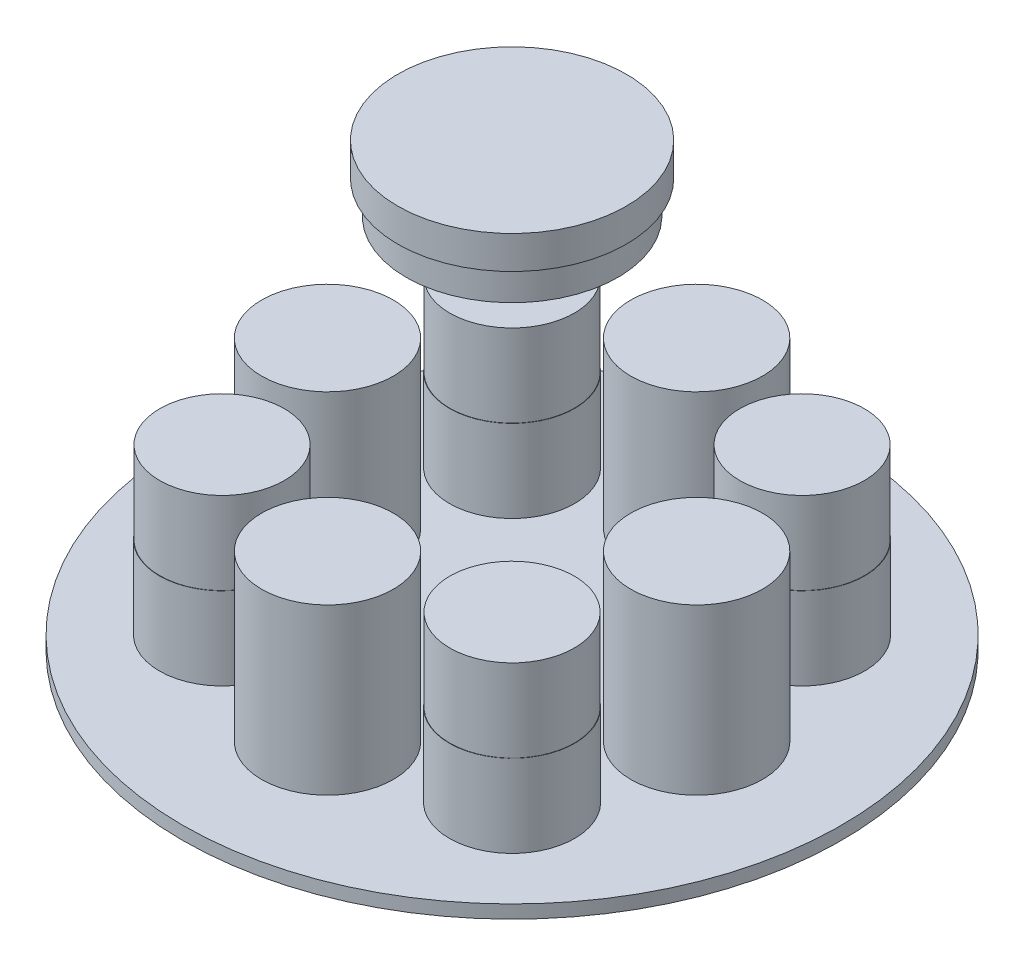
SolidWorks part; units mm, degrees
ref_plane "Front Plane" through (0, 0, 0) normal (0, 0, 1) x (1, 0, 0)
ref_plane "Top Plane" through (0, 0, 0) normal (0, 1, 0) x (1, 0, 0)
ref_plane "Right Plane" through (0, 0, 0) normal (1, 0, 0) x (0, 0, -1)
sketch "Sketch1" plane through (0, 0, 0) normal (0, 1, 0) x (1, 0, 0)
  circle A0 centre (0, 0) radius 50
  dimension "D1" = 100
extrude "Boss-Extrude1" add sketch "Sketch1" along normal blind 2 contours A0
sketch "Sketch2" plane through (0, 2, 0) normal (0, 1, 0) x (1, 0, 0)
  line L0 (-55, 0) -> (55, 0) construction
  circle A0 centre (28, 0) radius 10
  circle A1 centre (0, 28) radius 10
  circle A2 centre (-28, 0) radius 10
  circle A3 centre (0, -28) radius 10
  circle A5 centre (22, -22) radius 9.5
  circle A6 centre (-22, -22) radius 9.5
  circle A7 centre (22, 22) radius 9.5
  circle A8 centre (-22, 22) radius 9.5
  dimension "D1" = 20
  dimension "D2" = 20
  dimension "D3" = 20
  dimension "D4" = 20
  dimension "D9" = 19
  dimension "D10" = 19
  dimension "D5" = 28
  dimension "D6" = 28
  dimension "D7" = 28
  dimension "D8" = 28
  dimension "D11" = 22
  dimension "D12" = 22
  dimension "D13" = 22
  dimension "D14" = 22
extrude "Boss-Extrude2" add sketch "Sketch2" along normal blind 25 contours A1 | A0 | A3 | A2 region at (28, 2, 0) region at (0, 2, -28) region at (-28, 2, 0) region at (0, 2, 28)
extrude "Boss-Extrude3" add sketch "Sketch2<3>" along normal blind 12.5 contours A5 | A7 | A8 | A6 region at (22, 2, 22) region at (-22, 2, 22) region at (22, 2, -22) region at (-22, 2, -22)
sketch "Sketch2<3>" plane through (0, 2, 0) normal (0, 1, 0) x (1, 0, 0) same geometry as "Sketch2"
sketch "Sketch5" plane through (0, 14.5, 0) normal (0, 1, 0) x (1, 0, 0)
  circle A0 centre (-22, -22) radius 9.45
  circle A1 centre (22, 22) radius 9.45
  circle A2 centre (22, -22) radius 9.45
  circle A3 centre (-22, 22) radius 9.45
  dimension "D1" = 18.9
  dimension "D2" = 18.9
  dimension "D3" = 18.9
  dimension "D4" = 18.9
extrude "Boss-Extrude4" add sketch "Sketch5" along normal blind 12.5
ref_plane "Plane1" through (0, 57, 0) normal (0, 1, 0) x (1, 0, 0)
sketch "Sketch6" plane through (0, 57, 0) normal (0, 1, 0) x (1, 0, 0)
  circle A0 centre (0, 0) radius 16.0713
extrude "Boss-Extrude5" add sketch "Sketch6" along normal blind 5 separate body contours A0
sketch "Sketch7" plane through (0, 62, 0) normal (0, 1, 0) x (1, 0, 0)
  circle A0 centre (0, 0) radius 17.3454
extrude "Boss-Extrude6" add sketch "Sketch7" along normal blind 5
